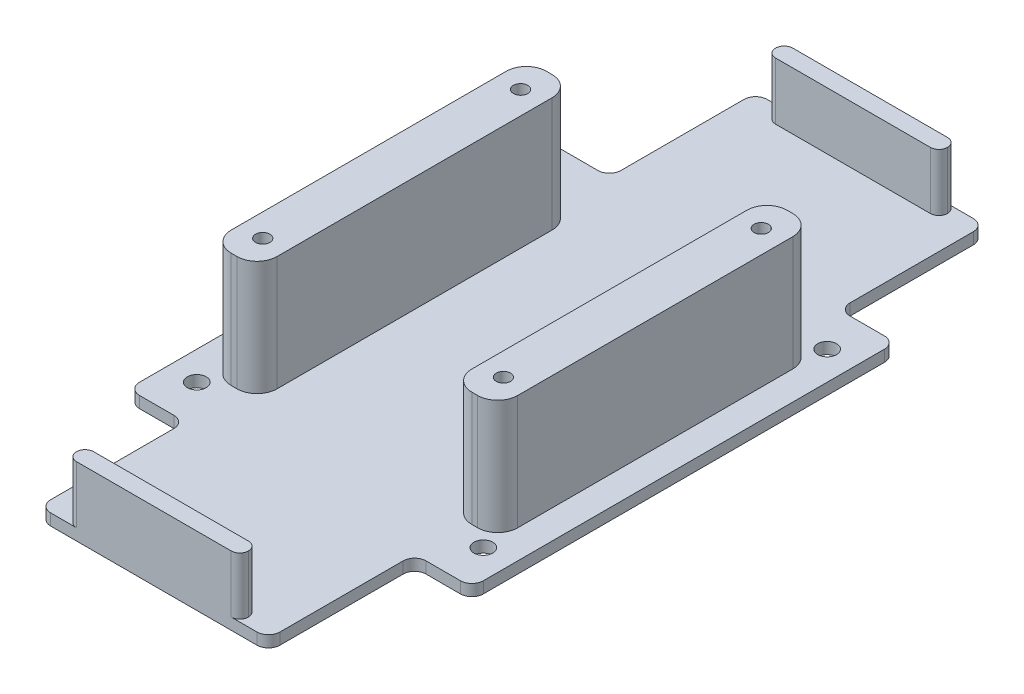
SolidWorks part; units mm, degrees
ref_plane "Спереди" through (0, 0, 0) normal (0, 0, 1) x (1, 0, 0)
ref_plane "Сверху" through (0, 0, 0) normal (0, 1, 0) x (1, 0, 0)
ref_plane "Справа" through (0, 0, 0) normal (1, 0, 0) x (0, 0, -1)
sketch "Эскиз1" plane through (0, 0, 0) normal (0, 1, 0) x (1, 0, 0)
  line L0 (0, 62.5) -> (0, -62.5) construction
  line L1 (-30, 62.5) -> (30, 62.5)
  line L2 (-30, 62.5) -> (-30, -62.5)
  line L3 (-30, -62.5) -> (30, -62.5)
  line L4 (30, 62.5) -> (30, -62.5)
  line L6 (-30, 0) -> (30, 0) construction
  point P8 (0, 0)
  dimension "D1" = 60
  dimension "D2" = 125
extrude "тело" add sketch "Эскиз1" along normal blind 2
sketch "Эскиз4" plane through (0, 2, 0) normal (0, 1, 0) x (1, 0, 0)
  line L0 (0, 62.5) -> (0, -62.5) construction
  line L1 (30, 62.5) -> (-30, 62.5) construction
  line L2 (-30, -62.5) -> (30, -62.5) construction
  line L3 (-25, 30) -> (25, -30) construction
  line L4 (-30, 62.5) -> (-30, -62.5) construction
  line L5 (-30, 0) -> (30, 0) construction
  line L6 (30, -62.5) -> (30, 62.5) construction
  line L7 (-25, 30) -> (25, 30) construction
  line L8 (-25, 30) -> (-25, -30) construction
  line L9 (-25, -30) -> (25, -30) construction
  line L10 (25, 30) -> (25, -30) construction
  circle A0 centre (-25, 30) radius 1.65
  circle A1 centre (25, 30) radius 1.65
  circle A2 centre (25, -30) radius 1.65
  circle A3 centre (-25, -30) radius 1.65
  point P20 (0, 0)
  dimension "D1" = 3.3
  dimension "D2" = 50
  dimension "D3" = 60
extrude "крепление к пластине" cut sketch "Эскиз4" against normal through all
sketch "Эскиз6" plane through (0, 2, 0) normal (0, 1, 0) x (1, 0, 0)
  line L0 (0, 62.5) -> (0, -62.5) construction
  line L1 (30, 62.5) -> (-30, 62.5) construction
  line L2 (-30, -62.5) -> (30, -62.5) construction
  line L3 (-25, 30) -> (-25, 37) construction
  line L4 (-30, 62.5) -> (-30, -62.5) construction
  line L5 (-30, 0) -> (30, 0) construction
  line L6 (30, -62.5) -> (30, 62.5) construction
  line L7 (-30, 62.5) -> (-20, 62.5)
  line L8 (-30, 62.5) -> (-30, 37)
  line L9 (-30, 37) -> (-20, 37)
  line L10 (-20, 62.5) -> (-20, 37)
  line L11 (30, 62.5) -> (20, 62.5)
  line L12 (30, 62.5) -> (30, 37)
  line L13 (30, 37) -> (20, 37)
  line L14 (20, 62.5) -> (20, 37)
  line L15 (30, -62.5) -> (20, -62.5)
  line L16 (30, -62.5) -> (30, -37)
  line L17 (30, -37) -> (20, -37)
  line L18 (20, -62.5) -> (20, -37)
  line L19 (-30, -62.5) -> (-20, -62.5)
  line L20 (-30, -62.5) -> (-30, -37)
  line L21 (-30, -37) -> (-20, -37)
  line L22 (-20, -62.5) -> (-20, -37)
  dimension "D1" = 7
extrude "вырезы под винты соседних плат" cut sketch "Эскиз6" against normal through all
sketch "Эскиз2" plane through (0, 2, 0) normal (0, 1, 0) x (1, 0, 0)
  line L0 (0, 62.5) -> (0, -62.5) construction
  line L3 (20, 62.5) -> (-20, 62.5) construction
  line L5 (-20, -62.5) -> (20, -62.5) construction
  line L7 (-30, 0) -> (30, 0) construction
  line L8 (-30, 37) -> (-30, -37) construction
  line L9 (30, -37) -> (30, 37) construction
  line L11 (-15, 62.5) -> (15, 62.5)
  line L12 (-15, 62.5) -> (-15, 59.5)
  line L13 (-15, 59.5) -> (15, 59.5)
  line L14 (15, 62.5) -> (15, 59.5)
  line L15 (-15, -62.5) -> (15, -62.5)
  line L16 (-15, -62.5) -> (-15, -59.5)
  line L17 (-15, -59.5) -> (15, -59.5)
  line L18 (15, -62.5) -> (15, -59.5)
  point P22 (0, 62.5)
  point P23 (0, -62.5)
  dimension "D1" = 119
  dimension "D2" = 30
extrude "выступы фиксации аккума" add sketch "Эскиз2" along normal blind 10
sketch "Эскиз9" plane through (0, 2, 0) normal (0, 1, 0) x (1, 0, 0)
  line L0 (0, 62.5) -> (0, -62.5) construction
  line L3 (-30, 0) -> (30, 0) construction
  line L5 (-30, 37) -> (-30, -37) construction
  line L6 (30, -37) -> (30, 37) construction
  line L7 (15, 62.5) -> (-15, 62.5) construction
  line L8 (-25, 27.5) -> (-17, 27.5)
  line L9 (-25, 27.5) -> (-25, -27.5)
  line L10 (-25, -27.5) -> (-17, -27.5)
  line L11 (-17, 27.5) -> (-17, -27.5)
  line L12 (25, 27.5) -> (17, 27.5)
  line L13 (25, 27.5) -> (25, -27.5)
  line L14 (25, -27.5) -> (17, -27.5)
  line L15 (17, 27.5) -> (17, -27.5)
  line L16 (-15, -62.5) -> (15, -62.5) construction
  point P20 (17, 0)
  point P21 (-17, 0)
  point P28 (0, 62.5)
  dimension "D1" = 34
  dimension "D2" = 55
  dimension "D3" = 8
extrude "выступы для крышки" add sketch "Эскиз9" along normal blind 20
sketch "Эскиз11" plane through (0, 22, 0) normal (0, 1, 0) x (1, 0, 0)
  line L0 (-21, 27.5) -> (-21, -27.5) construction
  line L1 (-17, 27.5) -> (-25, 27.5) construction
  line L2 (-25, -27.5) -> (-17, -27.5) construction
  line L4 (25, 27.5) -> (17, 27.5) construction
  line L5 (21, 27.5) -> (21, -27.5) construction
  line L6 (17, -27.5) -> (25, -27.5) construction
  line L8 (25, -27.5) -> (25, 27.5) construction
  line L9 (25, 0) -> (-25, 0) construction
  line L10 (-25, 27.5) -> (-25, -27.5) construction
  circle A0 centre (-21, 22.5) radius 1.25
  circle A1 centre (-21, -22.5) radius 1.25
  circle A2 centre (21, 22.5) radius 1.25
  circle A3 centre (21, -22.5) radius 1.25
  dimension "D2" = 2.5
  dimension "D1" = 45
extrude "отверстия под шурупы" cut sketch "Эскиз11" against normal blind 15
chamfer "Фаска1" [suppressed] distance 1.5 angle 45
fillet "Скругление1" radius 1.5 8 edges at (15, 7, -59.5) (15, 7, -62.5) (-15, 7, -62.5) (-15, 7, -59.5) (15, 7, 62.5) (15, 7, 59.5) (-15, 7, 59.5) (-15, 7, 62.5)
fillet "Скругление5" radius 2 12 edges at (-30, 1, 37) (-20, 1, 37) (-20, 1, 62.5) (-30, 1, -37) (-20, 1, -37) (-20, 1, -62.5) (20, 1, -62.5) (20, 1, -37) (30, 1, -37) (30, 1, 37) (20, 1, 37) (20, 1, 62.5)
fillet "Скругление6" radius 3.5 8 edges at (-25, 12, -27.5) (-17, 12, -27.5) (17, 12, -27.5) (25, 12, -27.5) (25, 12, 27.5) (17, 12, 27.5) (-17, 12, 27.5) (-25, 12, 27.5)
